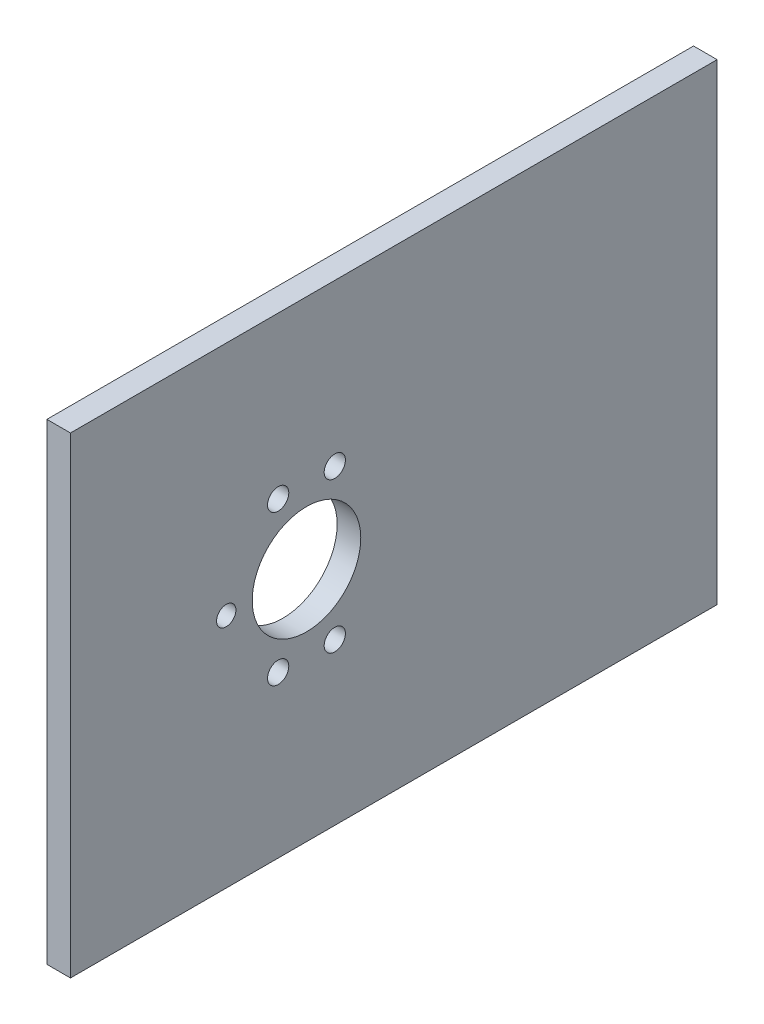
SolidWorks part; units mm, degrees
ref_plane "Ebene vorne" through (0, 0, 0) normal (0, 0, 1) x (1, 0, 0)
ref_plane "Ebene oben" through (0, 0, 0) normal (0, 1, 0) x (1, 0, 0)
ref_plane "Ebene rechts" through (0, 0, 0) normal (1, 0, 0) x (0, 0, -1)
sketch "Skizze1" plane through (0, 0, 0) normal (1, 0, 0) x (0, 0, -1)
  line L1 (-92, 59.9082) -> (-192, 59.9082)
  line L2 (-92, 59.9082) -> (-92, -40.0918) construction
  line L3 (-92, -40.0918) -> (-192, -40.0918)
  line L4 (-192, 59.9082) -> (-192, -40.0918)
  line L5 (-92, 59.9082) -> (-192, -40.0918) construction
  line L6 (-92, -40.0918) -> (-192, 59.9082) construction
  line L7 (-192, -40.0918) -> (-92, -40.0918) construction
  line L11 (-92, -40.0918) -> (-55, -40.0918)
  line L12 (-92, -40.0918) -> (-92, 59.9082) construction
  line L13 (-92, 59.9082) -> (-55, 59.9082)
  line L14 (-55, -40.0918) -> (-55, 59.9082)
  circle A0 centre (-142, 9.9082) radius 11.5
  circle A1 centre (-148, 25.8142) radius 2.25
  circle A2 centre (-136, 25.8142) radius 2.25
  circle A3 centre (-159, 9.9082) radius 2.05
  circle A4 centre (-148, -5.9978) radius 2.25
  circle A5 centre (-136, -5.9978) radius 2.25
  point P1 (-142, 9.9082)
  dimension "D3" = 23
  dimension "D4" = 4.5
  dimension "D6" = 4.1
  dimension "D1" = 100
  dimension "D2" = 100
  dimension "D5" = 87
extrude "Aufsatz-Linear austragen1" add sketch "Skizze1" along normal blind 5
